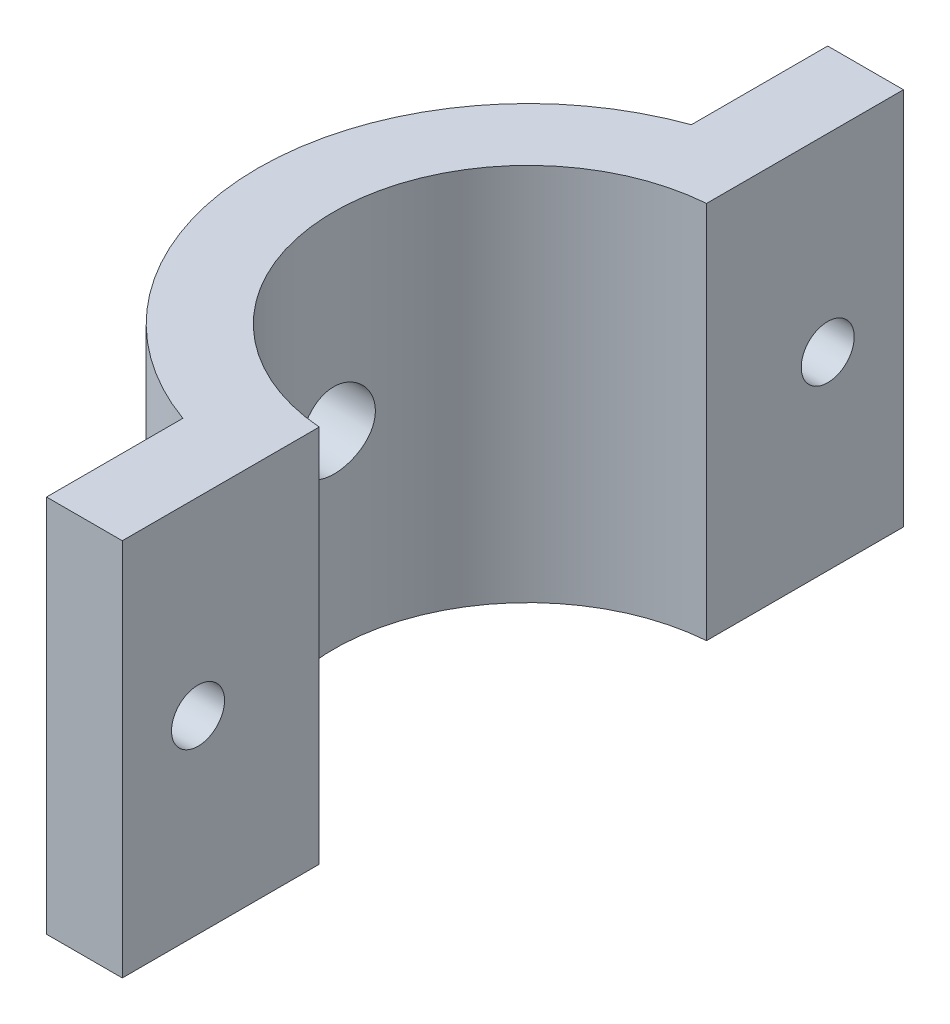
SolidWorks part; units mm, degrees
ref_plane "Front Plane" through (0, 0, 0) normal (0, 0, 1) x (1, 0, 0)
ref_plane "Top Plane" through (0, 0, 0) normal (0, 1, 0) x (1, 0, 0)
ref_plane "Right Plane" through (0, 0, 0) normal (1, 0, 0) x (0, 0, -1)
sketch "Sketch6" plane through (0, 0, 0) normal (0, -1, 0) x (1, 0, 0)
  line L5 (-1, 25.7848) -> (-1, 12.786)
  line L6 (-1, 25.7848) -> (-6, 25.7848)
  line L7 (-6, 25.7848) -> (-6, 16.7848)
  line L8 (-6, -16.7848) -> (-6, -25.7848)
  line L9 (-6, -25.7848) -> (-1, -25.7848)
  line L10 (-1, -25.7848) -> (-1, -12.786)
  line L11 (-12.825, 0) -> (-17.825, 0) construction
  arc A0 (-1, 12.786) -> (-1, -12.786) centre (0, 0) ccw
  arc A1 (-6, 16.7848) -> (-6, -16.7848) centre (0, 0) ccw
  dimension "D1" = 25.65
  dimension "D2" = 5
  dimension "D3" = 1
  dimension "D4" = 9
extrude "Boss-Extrude4" add sketch "Sketch6" along normal blind 25
sketch "Sketch7" plane through (-1, 0, 0) normal (1, 0, 0) x (0, 0, -1)
  line L0 (-20.7848, -25) -> (-20.7848, 0) construction
  line L3 (0, 0) -> (0, -25) construction
  line L6 (-25.7848, -12.5) -> (25.7848, -12.5) construction
  line L13 (-25.7848, -25) -> (-25.7848, 0) construction
  line L14 (25.7848, -25) -> (25.7848, 0) construction
  line L15 (-12.786, -25) -> (12.786, -25) construction
  circle A1 centre (-20.7848, -12.5) radius 1.75
  circle A2 centre (20.7848, -12.5) radius 1.75
  dimension "D1" = 3.5
  dimension "D2" = 5
extrude "Cut-Extrude1" cut sketch "Sketch7" against normal through all
sketch "Sketch8" plane through (0, 0, 0) normal (1, 0, 0) x (0, 0, -1)
  line L0 (-12.786, -25) -> (-12.786, 0) construction
  line L1 (12.786, -25) -> (12.786, 0) construction
  line L2 (-12.786, -12.5) -> (12.786, -12.5) construction
  circle A0 centre (0, -12.5) radius 5
  dimension "D1" = 10
extrude "Boss-Extrude5" add sketch "Sketch8" against normal blind 5 from offset 15 offset against normal yes
sketch "Sketch9" plane through (-20, 0, 0) normal (-1, 0, 0) x (0, 0, 1)
  circle A0 centre (0, -12.5) radius 2.5
  dimension "D1" = 5
extrude "Cut-Extrude2" cut sketch "Sketch9" against normal through all
